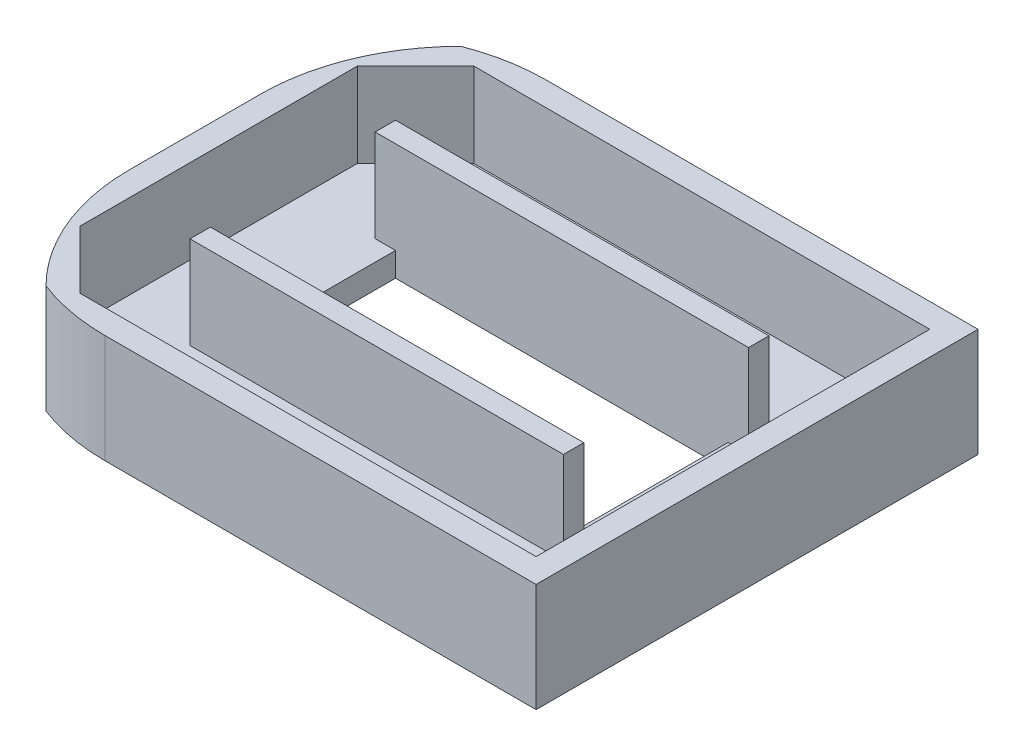
SolidWorks part; units mm, degrees
ref_plane "Front Plane" through (0, 0, 0) normal (0, 0, 1) x (1, 0, 0)
ref_plane "Top Plane" through (0, 0, 0) normal (0, 1, 0) x (1, 0, 0)
ref_plane "Right Plane" through (0, 0, 0) normal (1, 0, 0) x (0, 0, -1)
sketch "Sketch1" plane through (0, 0, 0) normal (0, 1, 0) x (1, 0, 0)
  line L0 (0, 46) -> (9, 55)
  line L1 (9, 0) -> (161, 0)
  line L2 (0, 9) -> (0, 46)
  line L3 (9, 55) -> (161, 55)
  line L4 (170, 9) -> (170, 46)
  line L5 (0, 9) -> (9, 0)
  line L6 (161, 55) -> (170, 46)
  line L7 (161, 0) -> (170, 9)
  point P0 (0, 0)
  point P1 (170, 55)
  point P2 (0, 55)
  point P3 (170, 0)
  dimension "D1" = 55
  dimension "D2" = 170
extrude "Boss-Extrude1" add sketch "Sketch1" along normal blind 30
sketch "Sketch2" plane through (0, 30, 0) normal (0, 1, 0) x (1, 0, 0)
  line L8 (3, 44.7574) -> (3, 10.2426)
  line L9 (10.2426, 3) -> (159.7574, 3)
  line L10 (167, 10.2426) -> (167, 44.7574)
  line L11 (159.7574, 52) -> (10.2426, 52)
  line L12 (3, 44.7574) -> (3, 10.2426)
  line L13 (10.2426, 3) -> (159.7574, 3)
  line L14 (167, 10.2426) -> (167, 44.7574)
  line L15 (159.7574, 52) -> (10.2426, 52)
  line L20 (3, 10.2426) -> (10.2426, 3)
  line L21 (3, 10.2426) -> (10.2426, 3)
  line L22 (159.7574, 3) -> (167, 10.2426)
  line L23 (159.7574, 3) -> (167, 10.2426)
  line L24 (167, 44.7574) -> (159.7574, 52)
  line L25 (167, 44.7574) -> (159.7574, 52)
  line L26 (10.2426, 52) -> (3, 44.7574)
  line L27 (10.2426, 52) -> (3, 44.7574)
  dimension "D1" = 3
shell "Shell2" thickness 3
extrude "Cut-Extrude2" cut sketch "Sketch2" against normal up to next
sketch "Length from bottom to Gear/Pin connection" plane through (0, 0, 0) normal (0, -1, 0) x (1, 0, 0)
  line L0 (0, -27.5) -> (25, -27.5) construction
  line L1 (0, -19.8) -> (0, 19.8) construction
  circle A0 centre (25, -27.5) radius 6.9102
  dimension "D1" = 25
sketch "Sketch4" plane through (0, 0, 0) normal (0, -1, 0) x (1, 0, 0)
  circle A0 centre (25, -27.5) radius 3.8
  dimension "D1" = 7.6
sketch "Outline of actual motor" plane through (0, 3, 0) normal (0, 1, 0) x (1, 0, 0)
  line L0 (15, 37.5) -> (55.9, 37.5) construction
  line L1 (55.9, 37.5) -> (55.9, 17.5) construction
  line L2 (55.9, 17.5) -> (15, 17.5) construction
  line L3 (15, 17.5) -> (15, 37.5) construction
  line L4 (55.2, 37.5) -> (15.7, 37.5) construction
  line L5 (15.7, 17.5) -> (55.2, 17.5) construction
  line L6 (55.9, 18.2) -> (55.9, 36.8) construction
  line L7 (15, 36.8) -> (15, 18.2) construction
  dimension "D1" = 0
  dimension "D2" = 0
  dimension "D3" = 0
  dimension "D4" = 0
sketch "Outline of motor press fit" plane through (0, 3, 0) normal (0, 1, 0) x (1, 0, 0)
  line L8 (15, 37.5) -> (55.9, 37.5) construction
  line L9 (14.75, 17.25) -> (56.15, 17.25)
  line L10 (14.75, 17.25) -> (14.75, 37.75)
  line L11 (14.75, 37.75) -> (56.15, 37.75)
  line L12 (56.15, 17.25) -> (56.15, 37.75)
  line L13 (55.9, 37.5) -> (55.9, 17.5) construction
  line L14 (55.9, 17.5) -> (15, 17.5) construction
  line L15 (15, 17.5) -> (15, 37.5) construction
  dimension "D1" = 0.25
  dimension "D2" = 0.25
  dimension "D3" = 0.25
  dimension "D4" = 0.25
sketch "Sketch16" plane through (0, 3, 0) normal (0, 1, 0) x (1, 0, 0)
  line L0 (18.21, 40.29) -> (52.69, 40.29)
  line L1 (52.69, 37.75) -> (18.21, 37.75)
  line L2 (18.21, 17.25) -> (52.69, 17.25)
  line L3 (52.69, 14.71) -> (18.21, 14.71)
  line L4 (14.75, 37.75) -> (12.21, 37.75)
  line L5 (12.21, 37.75) -> (58.69, 37.75)
  line L6 (58.69, 17.25) -> (56.15, 17.25)
  line L7 (12.21, 17.25) -> (14.75, 17.25)
  line L8 (12.21, 40.29) -> (18.21, 40.29) construction
  line L9 (12.21, 40.29) -> (12.21, 37.75) construction
  line L12 (12.21, 14.71) -> (58.69, 14.71)
  line L13 (58.69, 14.71) -> (58.69, 40.29)
  line L14 (58.69, 40.29) -> (12.21, 40.29)
  line L15 (12.21, 40.29) -> (12.21, 14.71)
  line L16 (12.21, 14.71) -> (18.21, 14.71)
  line L17 (58.69, 14.71) -> (58.69, 17.25)
  line L18 (58.69, 40.29) -> (52.69, 40.29)
  line L19 (12.21, 40.29) -> (12.21, 37.75)
  line L21 (14.75, 37.75) -> (56.15, 37.75) construction
  line L22 (18.21, 37.75) -> (14.75, 37.75)
  line L24 (35.45, 40.29) -> (35.45, 14.71) construction
  line L25 (12.21, 27.5) -> (58.69, 27.5) construction
  line L26 (18.21, 40.29) -> (12.21, 40.29)
  line L27 (12.21, 17.25) -> (12.21, 14.71)
  line L29 (58.69, 40.29) -> (58.69, 37.75)
  line L31 (52.69, 37.75) -> (56.15, 37.75)
  line L33 (52.69, 40.29) -> (58.69, 40.29)
  line L34 (52.69, 14.71) -> (58.69, 14.71)
  line L36 (52.69, 17.25) -> (56.15, 17.25)
  line L39 (58.69, 14.71) -> (58.69, 17.25)
  line L40 (18.21, 14.71) -> (12.21, 14.71)
  line L42 (18.21, 17.25) -> (14.75, 17.25)
  line L45 (12.21, 14.71) -> (12.21, 17.25)
  line L46 (58.69, 37.75) -> (58.69, 40.29)
  line L47 (52.69, 14.71) -> (58.69, 14.71)
  dimension "D2" = 6
  dimension "D1" = 2.54
extrude "Boss-Extrude5" add sketch "Sketch16" along normal blind 25.5 contours L29 L18 L0 L26 L19 L4 L5 L1 | L2 L42 L7 L27 L16 L3 L34 L17 L6 L36 region at (35.45, 3, -39.02) region at (35.45, 3, -15.98)
sketch "Sketch17" plane through (0, 28.5, 0) normal (0, 1, 0) x (1, 0, 0)
  line L0 (58.69, 40.29) -> (12.21, 40.29) construction
  line L1 (56.193, 40.29) -> (64.193, 40.29)
  line L2 (56.193, 40.29) -> (56.193, 14.71)
  line L3 (56.193, 14.71) -> (64.193, 14.71)
  line L4 (64.193, 40.29) -> (64.193, 14.71)
  line L5 (14.75, 37.75) -> (14.75, 40.29) construction
  line L6 (58.69, 40.29) -> (12.21, 40.29) construction
  line L8 (14.75, 40.29) -> (6.75, 40.29)
  line L9 (14.75, 40.29) -> (14.75, 14.71)
  line L10 (14.75, 14.71) -> (6.75, 14.71)
  line L11 (6.75, 40.29) -> (6.75, 14.71)
  dimension "D1" = 8
  dimension "D2" = 8
extrude "Boss-Extrude6" add sketch "Sketch17" against normal blind 5
sketch "Sketch18" plane through (0, 28.5, 0) normal (0, 1, 0) x (1, 0, 0)
  circle A0 centre (59.75, 32.5) radius 1.75
  circle A1 centre (59.75, 22.5) radius 1.75
  circle A2 centre (11.15, 22.5) radius 1.75
  circle A3 centre (11.15, 32.5) radius 1.75
  dimension "D1" = 3.5
  dimension "D2" = 3.5
  dimension "D3" = 3.5
  dimension "D4" = 3.5
extrude "Cut-Extrude3" cut sketch "Sketch18" against normal up to next
sketch "Sketch20" plane through (0, 30, 0) normal (0, 1, 0) x (1, 0, 0)
  line L1 (-8.4121, 65.847) -> (189.0699, 65.847)
  line L2 (-8.4121, 65.847) -> (-8.4121, -17.3253)
  line L3 (-8.4121, -17.3253) -> (189.0699, -17.3253)
  line L4 (189.0699, 65.847) -> (189.0699, -17.3253)
extrude "Cut-Extrude4" cut sketch "Sketch20" against normal offset from surface (16.5 mm away) 13.5 up to face at (85, 0, -27.5)
sketch "Sketch21" plane through (0, 0, 0) normal (0, 0, 1) x (1, 0, 0)
  line L0 (80.8737, 0) -> (80.8737, 13.5) construction
  line L1 (30.25, 0) -> (-30.25, 0) construction
  dimension "D1" = 13.5
extrude "Cut-Extrude5" cut sketch "Outline of motor press fit" against normal up to next
sketch "Sketch24" plane through (0, 13.5, 0) normal (0, 1, 0) x (1, 0, 0)
  line L1 (12.21, 40.29) -> (58.69, 40.29)
  line L2 (12.21, 40.29) -> (12.21, 37.75)
  line L3 (12.21, 37.75) -> (58.69, 37.75)
  line L4 (58.69, 40.29) -> (58.69, 37.75)
  line L5 (12.21, 17.25) -> (58.69, 17.25)
  line L6 (12.21, 17.25) -> (12.21, 14.71)
  line L7 (12.21, 14.71) -> (58.69, 14.71)
  line L8 (58.69, 17.25) -> (58.69, 14.71)
extrude "Boss-Extrude7" add sketch "Sketch24" along normal blind 1
sketch "Sketch25" plane through (0, 0, 0) normal (0, -1, 0) x (1, 0, 0)
  line L0 (0, -27.5) -> (70, -27.5) construction
  line L1 (70, 13.4618) -> (70, -84.299)
  line L2 (70, -84.299) -> (188.2354, -84.299)
  line L3 (188.2354, -84.299) -> (188.2354, 23.0423)
  line L4 (188.2354, 23.0423) -> (70, 19.7184)
  line L5 (70, 19.7184) -> (70, 13.4618)
  dimension "D1" = 70
extrude "Cut-Extrude6" cut sketch "Sketch25" against normal through all both and the other way through all
sketch "Sketch26" plane through (70, 0, 0) normal (1, 0, 0) x (0, 0, -1)
  line L1 (55, 13.5) -> (0, 13.5)
  line L2 (55, 13.5) -> (55, 0)
  line L3 (55, 0) -> (0, 0)
  line L4 (0, 13.5) -> (0, 0)
extrude "Boss-Extrude8" add sketch "Sketch26" against normal blind 3
fillet "Fillet1" radius 25 2 edges at (0, 6.75, -9) (0, 6.75, -46)
fillet "Fillet2" radius 25 2 edges at (9, 6.75, 0) (9, 6.75, -55)
equation "\"arm width\"=55"
equation "\"D1@Sketch1\"=\"arm width\""
equation "\"arm length\"=170"
equation "\"D2@Sketch1\"=\"arm length\""
equation "\"screwHoleDiameterMG996R\"= 3.5"
equation "\"D1@Sketch18\"=\"screwHoleDiameterMG996R\""
equation "\"D2@Sketch18\"=\"screwHoleDiameterMG996R\""
equation "\"D3@Sketch18\"=\"screwHoleDiameterMG996R\""
